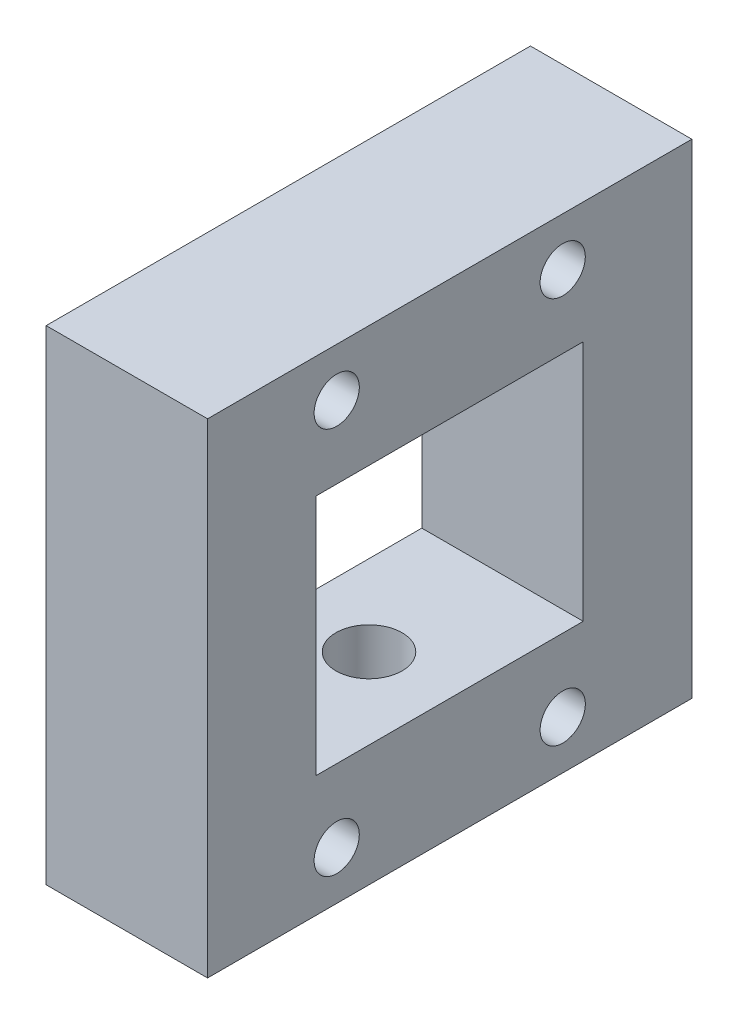
SolidWorks part; units mm, degrees
ref_plane "정면" through (0, 0, 0) normal (0, 0, 1) x (1, 0, 0)
ref_plane "윗면" through (0, 0, 0) normal (0, 1, 0) x (1, 0, 0)
ref_plane "우측면" through (0, 0, 0) normal (1, 0, 0) x (0, 0, -1)
sketch "스케치1" plane through (0, 0, 0) normal (1, 0, 0) x (0, 0, -1)
  line L1 (-15, 15) -> (15, 15)
  line L2 (-15, 15) -> (-15, -15)
  line L3 (-15, -15) -> (15, -15)
  line L4 (15, 15) -> (15, -15)
  line L5 (-15, 15) -> (15, -15) construction
  line L6 (-15, -15) -> (15, 15) construction
  line L7 (-8.2703, 7.5) -> (8.2703, 7.5)
  line L8 (-8.2703, 7.5) -> (-8.2703, -7.5)
  line L9 (-8.2703, -7.5) -> (8.2703, -7.5)
  line L10 (8.2703, 7.5) -> (8.2703, -7.5)
  line L11 (-8.2703, 7.5) -> (8.2703, -7.5) construction
  line L12 (-8.2703, -7.5) -> (8.2703, 7.5) construction
  point P0 (0, 0)
  point P6 (0, 0)
  dimension "D1" = 30
  dimension "D2" = 30
  dimension "D3" = 15
extrude "보스-돌출1" add sketch "스케치1" along normal blind 10
sketch "스케치4" plane through (0, 0, 0) normal (1, 0, 0) x (0, 0, -1)
  line L0 (0, 0) -> (-19.6569, 0) construction
  line L1 (-7, -12) -> (-7, -10.6) construction
  line L2 (0, 0) -> (0, -12) construction
  circle A0 centre (-7, -12) radius 1.4
  circle A1 centre (-7, 12) radius 1.4
  circle A2 centre (7, -12) radius 1.4
  circle A3 centre (7, 12) radius 1.4
  dimension "D1" = 2.8
  dimension "D2" = 12
  dimension "D3" = 7
extrude "컷-돌출3" cut sketch "스케치4" along normal through all
sketch "스케치5" plane through (0, 0, 0) normal (0, 1, 0) x (1, 0, 0)
  line L0 (5, 15) -> (5, -15) construction
  line L1 (10, 15) -> (0, 15) construction
  line L2 (10, -15) -> (0, -15) construction
  circle A0 centre (5, 0) radius 2.05
  dimension "D1" = 4.1
sketch "스케치8" plane through (0, 0, 0) normal (-1, 0, 0) x (0, 0, 1)
  circle A0 centre (-7, 12) radius 2.9
  circle A1 centre (7, 12) radius 2.9
  circle A2 centre (-7, -12) radius 2.9
  circle A3 centre (7, -12) radius 2.9
  dimension "D1" = 5.8
  dimension "D2" = 5.8
  dimension "D3" = 5.8
  dimension "D4" = 5.8
extrude "컷-돌출6" cut sketch "스케치8" against normal blind 2
chamfer "모따기1" distance 2 distance2 1.6 4 edges at (2, -12, 9.9) (2, 12, 9.9) (2, 12, -4.1) (2, -12, -4.1) first distance on face at (2, -12, 9.9) first distance on face at (2, 12, 9.9) first distance on face at (2, 12, -4.1) first distance on face at (2, -12, -4.1)
extrude "컷-돌출7" cut sketch "스케치5" against normal blind 20 contours A0
sketch "스케치9" plane through (0, 7.5, 0) normal (0, -1, 0) x (1, 0, 0)
  circle A0 centre (5, 0) radius 2.8
  circle A1 centre (5, 0) radius 2.2
  dimension "D1" = 5.6
  dimension "D2" = 4.4
extrude "컷-돌출8" cut sketch "스케치9" against normal blind 5
fillet "필렛1" radius 1 1 edges at (5, 7.5, -2.2)
